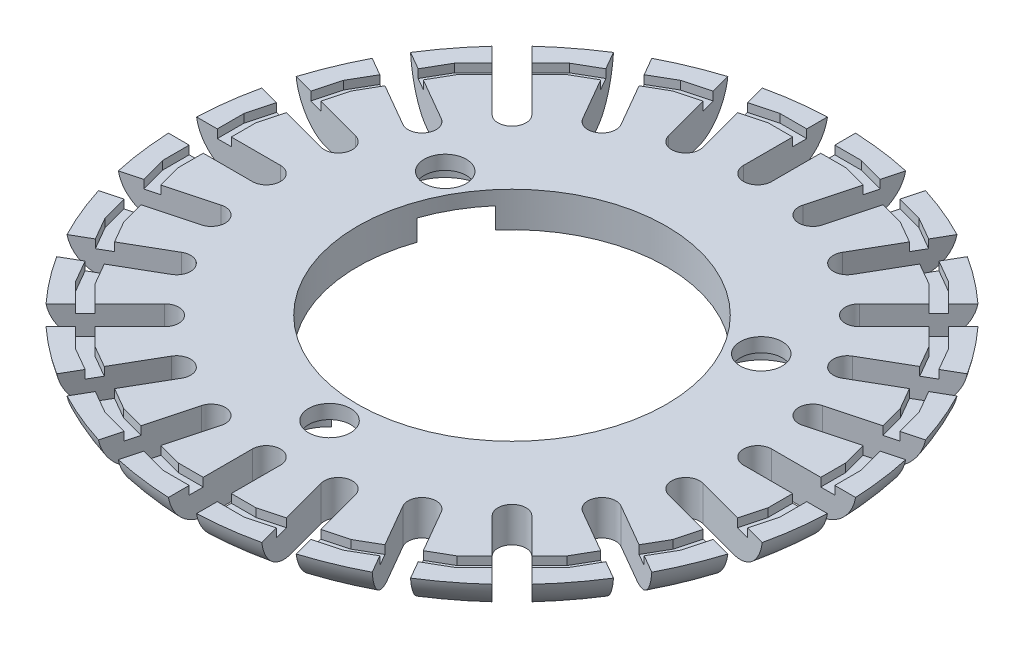
SolidWorks part; units mm, degrees
ref_plane "Plano frontal" through (0, 0, 0) normal (0, 0, 1) x (1, 0, 0)
ref_plane "Plano superior" through (0, 0, 0) normal (0, 1, 0) x (1, 0, 0)
ref_plane "Plano direito" through (0, 0, 0) normal (1, 0, 0) x (0, 0, -1)
sketch "Esboço1" plane through (0, 0, 0) normal (0, 1, 0) x (1, 0, 0)
  circle A0 centre (0, 0) radius 23.5
  dimension "D1" = 47
extrude "Ressalto-extrusão1" add sketch "Esboço1" along normal blind 2.5
fillet "Filete1" radius 3 1 edges at (0, 0, 23.5)
sketch "Esboço2" plane through (0, 2.5, 0) normal (0, 1, 0) x (1, 0, 0)
  line L0 (0, 0) -> (0, 23.9078) construction
  line L2 (1, 17.5) -> (1, 23.5)
  line L3 (1, 23.5) -> (-1, 23.5)
  line L4 (0, 23.5) -> (7.8408, 23.5) construction
  line L5 (-1, 17.5) -> (-1, 23.5)
  arc A0 (-1, 17.5) -> (1, 17.5) centre (0, 17.5) ccw
  circle A3 centre (0, 0) radius 23.5 construction
  point P12 (0, 16.5)
  dimension "D2" = 6
  dimension "D1" = 1
extrude "Corte-extrusão1" cut sketch "Esboço2" against normal through all
pattern_circular "PadrãoCircular1" count 24 over 360 about axis through (0, 2.5, 0) along (0, 1, 0) of "Corte-extrusão1"
sketch "Esboço4" plane through (0, 2.5, 0) normal (0, 1, 0) x (1, 0, 0)
  line L0 (0, 0) -> (-3.0674, 23.299) construction
  line L1 (0, 0) -> (3.0674, 23.299) construction
  line L2 (-2.8964, 22) -> (2.8964, 22)
  line L3 (2.8964, 22) -> (2.7647, 21)
  line L4 (2.7647, 21) -> (-2.7647, 21)
  line L5 (-2.7647, 21) -> (-2.8964, 22)
  arc A2 (5.1108, 22.9375) -> (1, 23.4787) centre (0, 0) ccw construction
  arc A3 (-1, 23.4787) -> (-5.1108, 22.9375) centre (0, 0) ccw construction
  dimension "D1" = 1
  dimension "D2" = 21
extrude "Corte-extrusão2" cut sketch "Esboço4" against normal blind 0.6
pattern_circular "PadrãoCircular2" count 24 over 360 about axis through (0, 2.5, 0) along (0, 1, 0) of "Corte-extrusão2"
sketch "Esboço5" plane through (0, 2.5, 0) normal (0, 1, 0) x (1, 0, 0)
  circle A0 centre (0, 0) radius 11
  dimension "D1" = 22
extrude "Corte-extrusão3" cut sketch "Esboço5" against normal through all
sketch "Esboço6" plane through (0, 2.5, 0) normal (0, 1, 0) x (1, 0, 0)
  circle A4 centre (-11.2583, 6.5) radius 1.5
  circle A5 centre (11.2583, 6.5) radius 1.5
  circle A6 centre (0, -13) radius 1.5
  dimension "D5" = 3
extrude "Corte-extrusão5" cut sketch "Esboço6" against normal blind 2.5
sketch "Esboço8" plane through (0, 0, 0) normal (0, -1, 0) x (-1, 0, 0)
  circle A0 centre (11.2583, 6.5) radius 3
  circle A1 centre (-11.2583, 6.5) radius 3
  circle A2 centre (0, -13) radius 3
  dimension "D1" = 6
extrude "Corte-extrusão6" cut sketch "Esboço8" against normal blind 1.5
